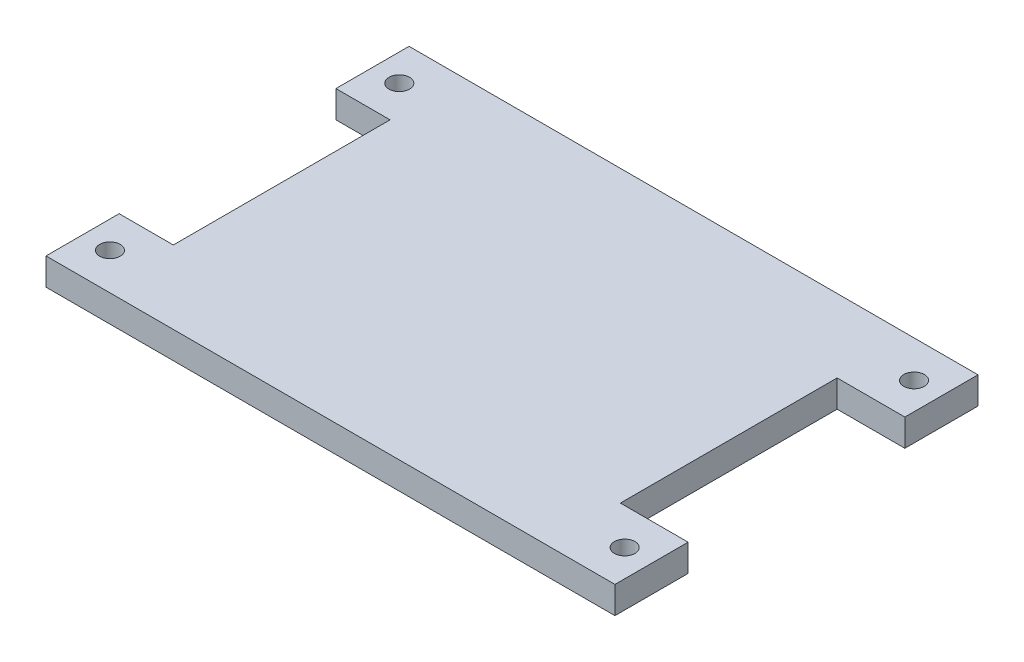
SolidWorks part; units mm, degrees
material "1060 Alloy"
ref_plane "Front Plane" through (0, 0, 0) normal (0, 0, 1) x (1, 0, 0)
ref_plane "Top Plane" through (0, 0, 0) normal (0, 1, 0) x (1, 0, 0)
ref_plane "Right Plane" through (0, 0, 0) normal (1, 0, 0) x (0, 0, -1)
sketch "Sketch1" plane through (0, 0, 0) normal (0, 1, 0) x (1, 0, 0)
  line L1 (-45.1884, 47.6545) -> (88.1616, 47.6545)
  line L2 (-45.1884, 47.6545) -> (-45.1884, -37.4355)
  line L3 (-45.1884, -37.4355) -> (88.1616, -37.4355)
  line L4 (88.1616, 47.6545) -> (88.1616, -37.4355)
  dimension "D1" = 133.35
  dimension "D2" = 85.09
extrude "Boss-Extrude1" add sketch "Sketch1" along normal blind 6.35
sketch "Sketch4" plane through (0, 6.35, 0) normal (0, 1, 0) x (1, 0, 0)
  line L0 (88.1616, -37.4355) -> (88.1616, 47.6545) construction
  line L1 (88.1616, 30.5095) -> (72.2866, 30.5095)
  line L2 (88.1616, 30.5095) -> (88.1616, -20.2905)
  line L3 (88.1616, -20.2905) -> (72.2866, -20.2905)
  line L4 (72.2866, 30.5095) -> (72.2866, -20.2905)
  line L5 (21.4866, 47.6545) -> (21.4866, -37.4355) construction
  line L6 (88.1616, 47.6545) -> (-45.1884, 47.6545) construction
  line L7 (-45.1884, -37.4355) -> (88.1616, -37.4355) construction
  line L12 (-45.1884, 5.1095) -> (88.1616, 5.1095) construction
  line L13 (-45.1884, 30.5095) -> (-45.1884, -20.2905)
  line L14 (-45.1884, 30.5095) -> (-32.4884, 30.5095)
  line L15 (-45.1884, -20.2905) -> (-32.4884, -20.2905)
  line L16 (-32.4884, 30.5095) -> (-32.4884, -20.2905)
  line L17 (-45.1884, 47.6545) -> (-45.1884, -37.4355) construction
  dimension "D1" = 15.875
  dimension "D2" = 50.8
  dimension "D3" = 12.7
  dimension "D4" = 50.8
extrude "Cut-Extrude8" cut sketch "Sketch4" against normal through all
sketch "Sketch2" plane through (0, 6.35, 0) normal (0, 1, 0) x (1, 0, 0)
  line L0 (88.1616, -37.4355) -> (88.1616, -20.2905) construction
  line L1 (-45.1884, -37.4355) -> (88.1616, -37.4355) construction
  line L2 (21.4866, 47.6545) -> (21.4866, -37.4355) construction
  line L3 (88.1616, 47.6545) -> (-45.1884, 47.6545) construction
  circle A0 centre (81.8116, -28.7995) radius 2.413
  circle A1 centre (81.8116, 39.0185) radius 2.413
  circle A4 centre (-38.8384, 39.0185) radius 2.413
  circle A5 centre (-38.8384, -28.7995) radius 2.413
  point P0 (81.8116, -28.7995)
  point P2 (81.8116, 39.0185)
  point P20 (-38.8384, 39.0185)
  point P21 (-38.8384, -28.7995)
  dimension "D5" = 4.826
  dimension "D1" = 6.35
  dimension "D3" = 8.636
  dimension "D4" = 8.636
extrude "Cut-Extrude1" cut sketch "Sketch2" against normal through all
